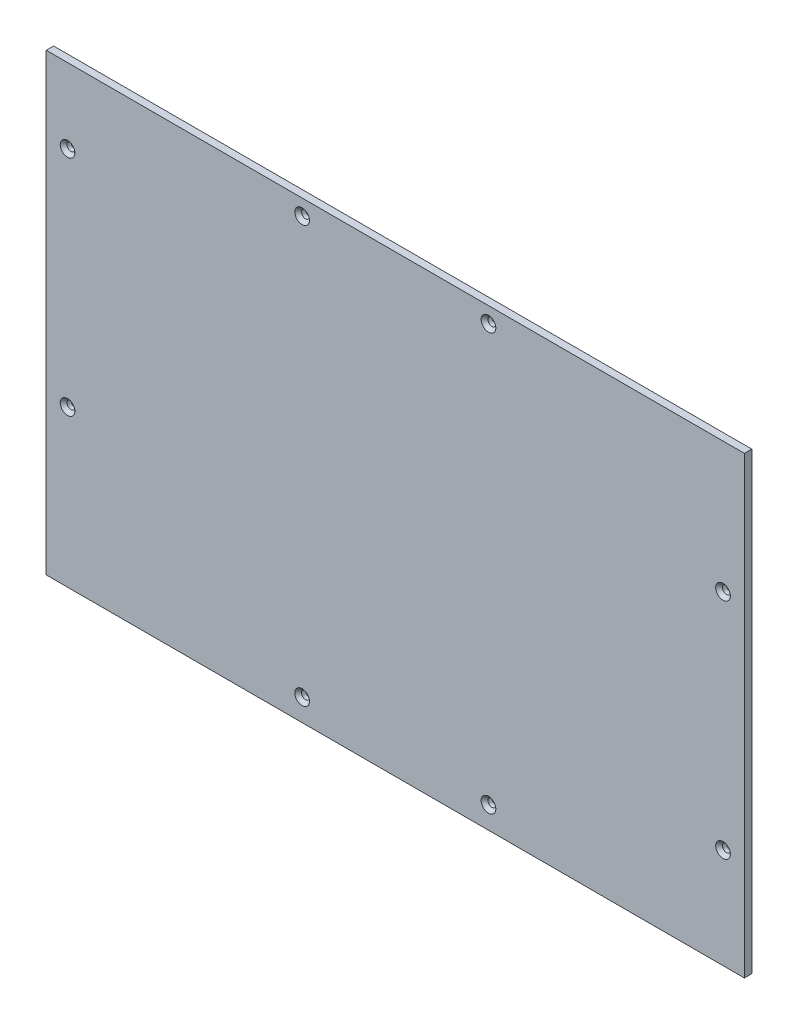
SolidWorks part; units mm, degrees
material "ABS"
ref_plane "X-Y Datum" through (0, 0, 0) normal (0, 0, 1) x (1, 0, 0)
ref_plane "X-Z Datum" through (0, 0, 0) normal (0, 1, 0) x (1, 0, 0)
ref_plane "Y-Z Datum" through (0, 0, 0) normal (1, 0, 0) x (0, 0, -1)
sketch "Sketch1" plane through (0, 0, 0) normal (0, 0, 1) x (1, 0, 0)
  line L0 (-149.85, 97.5219) -> (-149.85, -97.5219)
  line L1 (-149.85, 97.5219) -> (149.85, 97.5219)
  line L2 (-149.85, 97.5219) -> (-149.85, -97.5219)
  line L3 (-149.85, -97.5219) -> (149.85, -97.5219)
  line L4 (149.85, 97.5219) -> (149.85, -97.5219)
  line L5 (-149.85, 97.5219) -> (149.85, -97.5219) construction
  line L6 (-149.85, -97.5219) -> (149.85, 97.5219) construction
  line L7 (-149.85, -97.5219) -> (149.85, -97.5219)
  line L8 (149.85, 97.5219) -> (149.85, -97.5219)
  line L9 (-149.85, 97.5219) -> (149.85, 97.5219)
  circle A0 centre (-139.075, -86.7469) radius 10.775
  circle A1 centre (-115.075, -86.7469) radius 10.775 construction
  circle A2 centre (-127.075, -63.7469) radius 10.775
  point P0 (0, 0)
  dimension "D1" = 21.55
  dimension "D2" = 24
  dimension "D3" = 23
  dimension "D4" = 12
  dimension "D5" = 195.0437
  dimension "D6" = 299.7
  dimension "D7" = 0
extrude "Boss-Extrude1" add sketch "Sketch1" along normal blind 3.175 contours A0 L3 L4 L1 L2 A2 | A2 | A0 | A0 L2 L3 | L9 L0 L7 L8 L1 L4 L3 L2 region at (1.7461, 0.9924, 0) region at (-147.4432, -95.1151, 0) region at (-139.075, -86.7469, 0) region at (-127.075, -63.7469, 0)
sketch "Sketch2" plane through (0, 0, 3.175) normal (0, 0, 1) x (1, 0, 0)
  point P0 (140.6875, -54.525)
  point P1 (140.6875, 41.475)
  point P3 (-40, 90.775)
  point P5 (40, 90.775)
  point P7 (-140.6875, 65.475)
  point P9 (-140.6875, -30.525)
  point P11 (40, -88.0307)
  point P13 (-40, -88.0307)
hole_wizard "CSK for M3 Flat Head Machine Screw1" positions "Sketch3" profile "Sketch4" countersink size "M3" standard "ANSI Metric" end condition through all
sketch "Sketch3" plane through (0, 0, 3.175) normal (0, 0, 1) x (1, 0, 0)
  point P0 (-40, 90.775)
  point P3 (140.6875, 41.475)
  point P6 (140.6875, -54.525)
  point P9 (40, -88.0307)
  point P12 (-40, -88.0307)
  point P15 (-140.6875, -30.525)
  point P18 (-140.6875, 65.475)
  point P21 (40, 90.775)
sketch "Sketch4" plane through (-40, 90.775, 3.175) normal (1, 0, 0) x (0, -1, 0)
  line L0 (0, 0) -> (0, 3.175)
  line L1 (0, 3.175) -> (1.7, 3.175)
  line L2 (1.7, 3.175) -> (1.7, 1.45)
  line L3 (1.7, 1.45) -> (3.15, 0)
  line L5 (3.15, 0) -> (0, 0)
  line L6 (-1.7, 1.45) -> (-3.15, 0) construction
  line L11 (0, -6.35) -> (0, 107.95) construction
  dimension "Thru Hole Dia." = 3.4
  dimension "Thru Hole Depth" = 3.175
  dimension "Near C'Sink Dia." = 6.3
  dimension "Near C'Sink Angle" = 90
